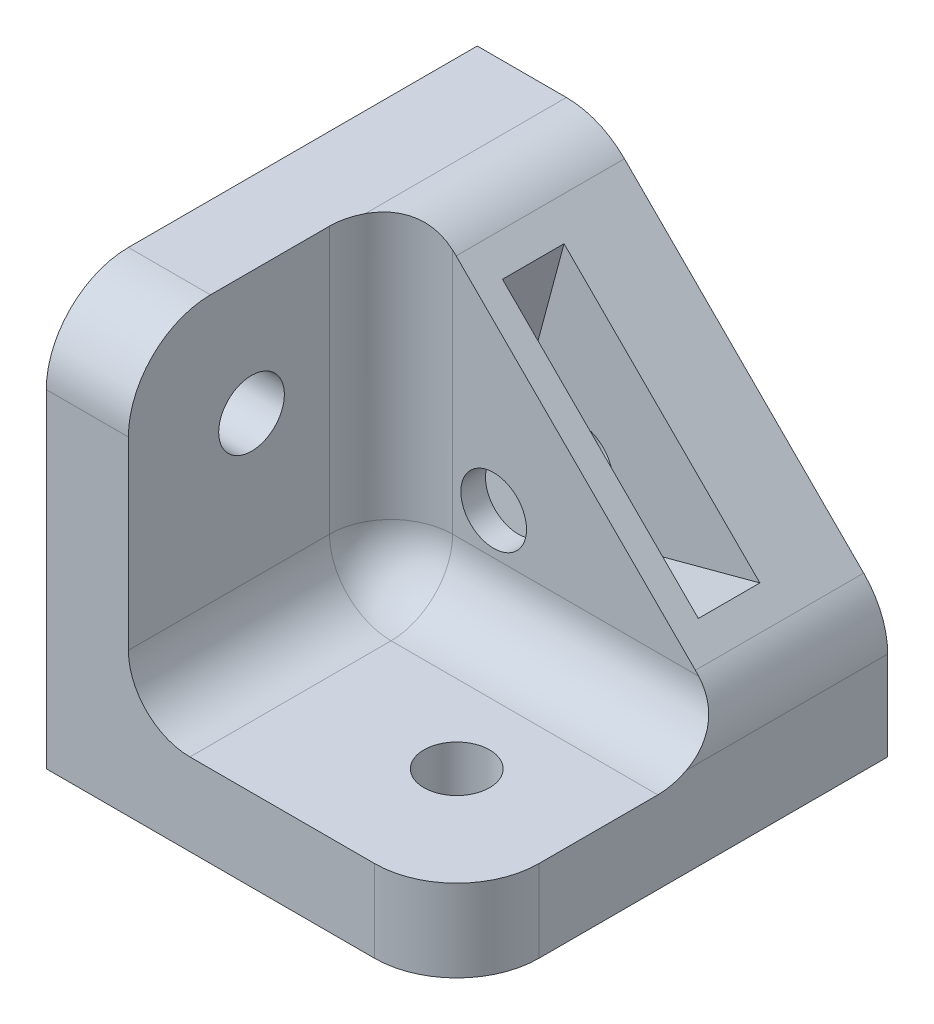
SolidWorks part; units mm, degrees
material "PET-G"
ref_plane "Front Plane" through (0, 0, 0) normal (0, 0, 1) x (1, 0, 0)
ref_plane "Top Plane" through (0, 0, 0) normal (0, 1, 0) x (1, 0, 0)
ref_plane "Right Plane" through (0, 0, 0) normal (1, 0, 0) x (0, 0, -1)
sketch "Sketch4" plane through (0, 0, 0) normal (0, 0, 1) x (1, 0, 0)
  line L2 (0, 0) -> (0, 20)
  line L3 (0, 20) -> (4, 20)
  line L4 (4, 4) -> (4, 20)
  line L5 (0, 0) -> (20, 0)
  line L7 (4, 4) -> (20, 4)
  line L8 (20, 0) -> (20, 4)
  line L9 (4, 20) -> (6, 20)
  line L10 (6, 20) -> (20, 6)
  line L11 (20, 6) -> (20, 4)
  dimension "D1" = 4
  dimension "D2" = 4
  dimension "D3" = 20
  dimension "D4" = 20
  dimension "D5" = 2
  dimension "D6" = 2
extrude "Base" add sketch "Sketch4" along normal blind 8.2 separate body contours L5 L8 L7 L4 L3 L2 | L4 L7 region at (0.2828, 10, 0) region at (9.9325, 9.9325, 0)
extrude "Sides" add sketch "Sketch4<4>" along normal blind 21 contours L5 L8 L7 L4 L3 L2 region at (0.2828, 10, 0)
sketch "Sketch4<4>" plane through (0, 0, 0) normal (0, 0, 1) x (1, 0, 0) same geometry as "Sketch4"
hole_wizard "Ø3.2 (3.2) Mounting Holes" positions "3DSketch2" profile "Sketch6" hole size "Ø3.2" standard "ANSI Metric" end condition through all
sketch3d "3DSketch2"
  line L0 (0, 0, 21) -> (0, 0, 0) construction
  line L1 (0, 0, 0) -> (20, 0, 0) construction
  line L2 (0, 0, 0) -> (0, 20, 0) construction
  point P0 (14, 0, 15)
  point P2 (0, 14, 15)
  point P4 (9, 9, 0)
  dimension "D1" = 14
  dimension "D2" = 14
  dimension "D3" = 15
  dimension "D4" = 15
  dimension "D5" = 9
  dimension "D6" = 9
sketch "Sketch6" plane through (14, 0, 15) normal (1, 0, 0) x (0, 0, -1)
  line L0 (0, 0) -> (0, 20)
  line L1 (0, 20) -> (1.6, 20)
  line L2 (1.6, 20) -> (1.6, 0)
  line L5 (1.6, 0) -> (0, 0)
  line L11 (0, -6.35) -> (0, 107.95) construction
  dimension "Thru Hole Dia." = 3.2
  dimension "Thru Hole Depth" = 20
fillet "InsideFillet" radius 3 3 edges at (12, 4, 8.2) (4, 4, 14.6) (4, 12, 8.2)
fillet "OutsideFillet" radius 4 4 edges at (6, 20, 4.1858) (20, 6, 4.1858) (20, 2, 21) (2, 20, 21)
sketch "Sketch7" plane through (0, 0, 0) normal (0, 0, -1) x (-1, 0, 0)
  line L0 (-8.2284, 17.7716) -> (-5.6412, 8.1161)
  line L1 (-7.1716, 18.8284) -> (-18.8284, 7.1716) construction
  line L2 (-5.6412, 8.1161) -> (-8.1161, 5.6412)
  line L3 (-8.1161, 5.6412) -> (-17.7716, 8.2284)
  line L4 (-13, 13) -> (-6.8787, 6.8787) construction
  line L5 (-8.2284, 17.7716) -> (-17.7716, 8.2284)
  circle A0 centre (-9, 9) radius 1.6 construction
  dimension "D1" = 60
  dimension "D2" = 3.5
  dimension "D3" = 3
extrude "NutSlot" cut sketch "Sketch7" against normal blind 3 from offset 4 offset against normal yes
equation "\"D2@Sketch4\"=\"D1@Sketch4\""
equation "\"D4@Sketch4\"=\"D3@Sketch4\""
equation "\"D6@Sketch4\"=\"D5@Sketch4\""
